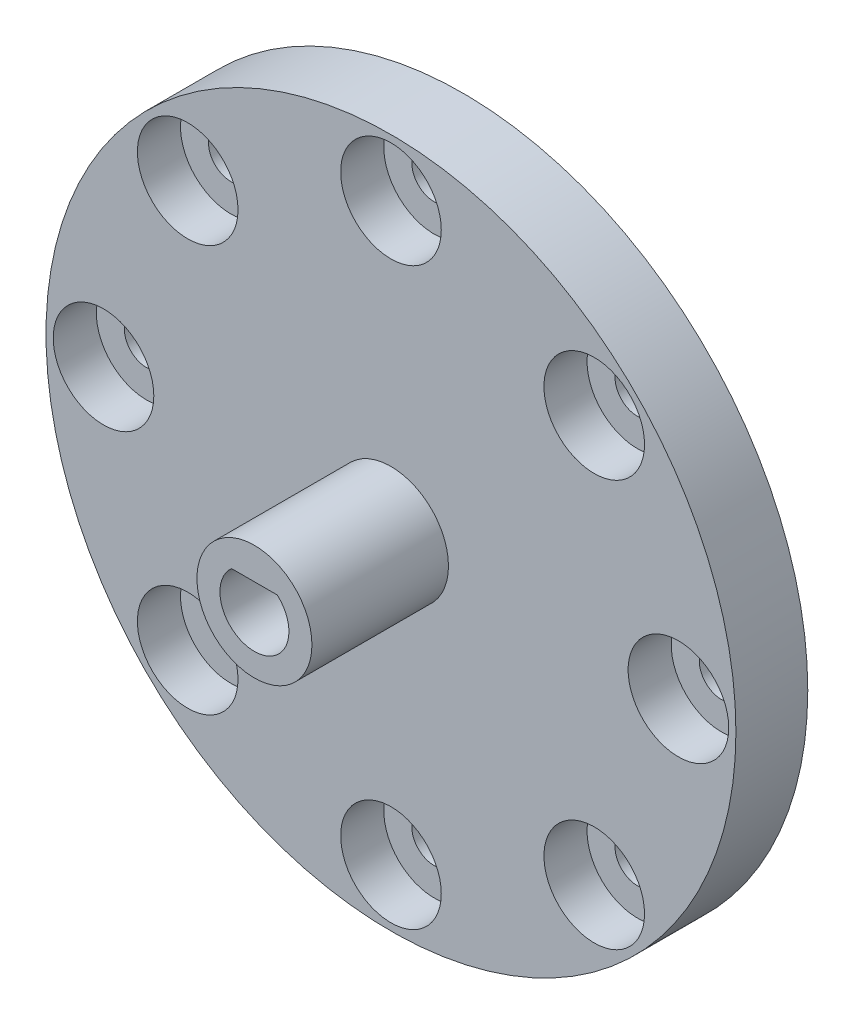
SolidWorks part; units mm, degrees
ref_plane "Front Plane" through (0, 0, 0) normal (0, 0, 1) x (1, 0, 0)
ref_plane "Top Plane" through (0, 0, 0) normal (0, 1, 0) x (1, 0, 0)
ref_plane "Right Plane" through (0, 0, 0) normal (1, 0, 0) x (0, 0, -1)
ref_axis "Axis1" through (0, 0, 5.5) along (0, 0, -1)
sketch "Sketch6" plane through (0, 0, 0) normal (0, 0, 1) x (1, 0, 0)
  circle A0 centre (0, 0) radius 24
extrude "Boss-Extrude1" add sketch "Sketch6" along normal blind 5
sketch "Sketch8" plane through (0, 0, 0) normal (0, 0, -1) x (-1, 0, 0)
  line L0 (0, 20) -> (0, 0) construction
  circle A0 centre (0, 20) radius 1.55
  circle A1 centre (14.1421, 14.1421) radius 1.55
  circle A2 centre (20, 0) radius 1.55
  circle A3 centre (14.1421, -14.1421) radius 1.55
  circle A4 centre (0, -20) radius 1.55
  circle A5 centre (-14.1421, -14.1421) radius 1.55
  circle A6 centre (-20, 0) radius 1.55
  circle A7 centre (-14.1421, 14.1421) radius 1.55
  dimension "D1" = 8
extrude "Cut-Extrude6" cut sketch "Sketch8" against normal up to surface (5 mm away) up to face at (24, 0, 5)
sketch "Sketch10" plane through (0, 0, 5) normal (0, 0, 1) x (1, 0, 0)
  circle A0 centre (0, 0) radius 4
extrude "Boss-Extrude2" add sketch "Sketch10" along normal blind 9.5
sketch "Sketch11" plane through (0, 0, 5) normal (0, 0, 1) x (1, 0, 0)
  circle A0 centre (0, 20) radius 3.5
  circle A1 centre (14.1421, 14.1421) radius 3.5
  circle A2 centre (20, 0) radius 3.5
  circle A3 centre (14.1421, -14.1421) radius 3.5
  circle A4 centre (0, -20) radius 3.5
  circle A5 centre (-14.1421, -14.1421) radius 3.5
  circle A6 centre (-20, 0) radius 3.5
  circle A7 centre (-14.1421, 14.1421) radius 3.5
  point P19 (0, 0)
  dimension "D1" = 8
extrude "Cut-Extrude8" cut sketch "Sketch11" against normal blind 3
sketch "Sketch12" plane through (0, 0, 14.5) normal (0, 0, 1) x (1, 0, 0)
  line L0 (0, 0) -> (0, 1.8) construction
  line L1 (-1.5875, 1.8) -> (1.5875, 1.8)
  circle A0 centre (0, 0) radius 2.4 construction
  arc A1 (-1.5875, 1.8) -> (1.5875, 1.8) centre (0, 0) ccw
  point P7 (0, 1.8)
extrude "Cut-Extrude9" cut sketch "Sketch12" against normal blind 8
